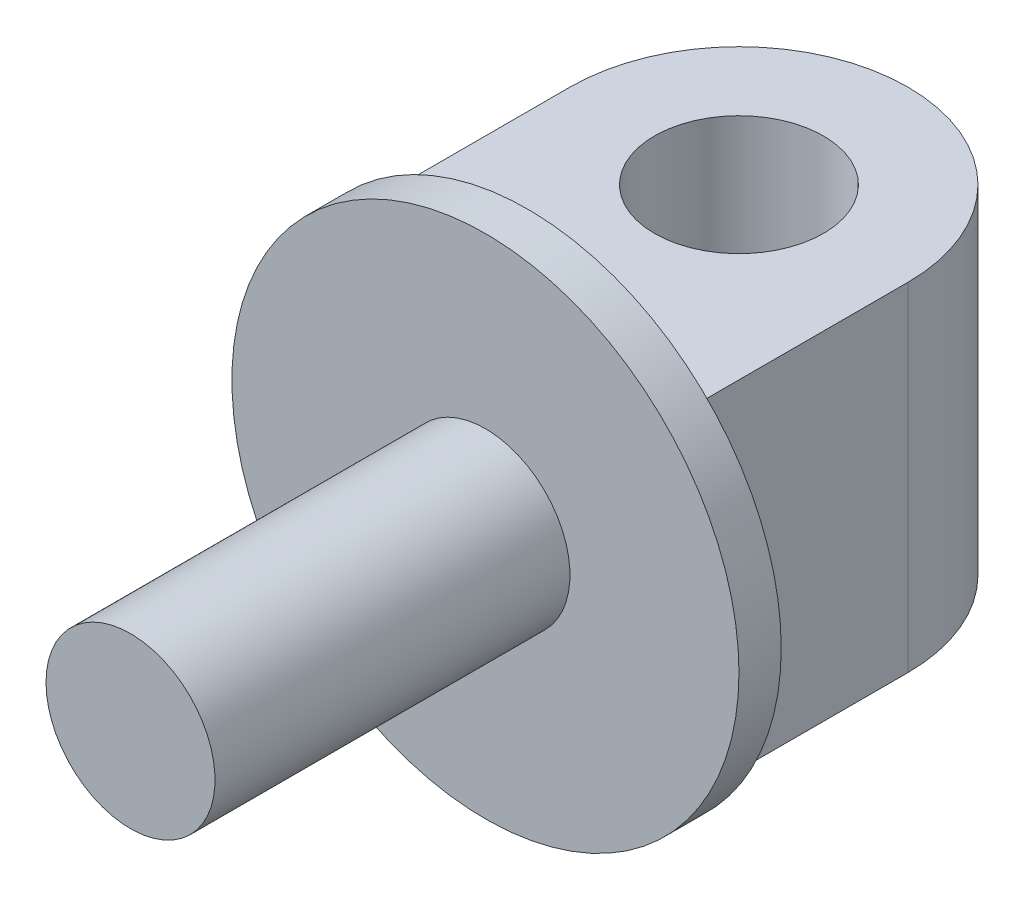
SolidWorks part; units mm, degrees
ref_plane "Front Plane" through (0, 0, 0) normal (0, 0, 1) x (1, 0, 0)
ref_plane "Top Plane" through (0, 0, 0) normal (0, 1, 0) x (1, 0, 0)
ref_plane "Right Plane" through (0, 0, 0) normal (1, 0, 0) x (0, 0, -1)
sketch "Cuff Stopper Sketch" plane through (0, 0, 0) normal (0, 0, 1) x (1, 0, 0)
  circle A0 centre (0, 0) radius 30
  dimension "D1" = 60
extrude "Cuff Stopper Extrude" add sketch "Cuff Stopper Sketch" against normal blind 5
sketch "Cuff Pin Sketch" plane through (0, 0, 0) normal (0, 0, 1) x (1, 0, 0)
  circle A0 centre (0, 0) radius 10
  dimension "D1" = 20
extrude "Cuff Pin Extrude" add sketch "Cuff Pin Sketch" along normal blind 42
sketch "Support Sketch" plane through (0, 0, -5) normal (0, 0, -1) x (-1, 0, 0)
  line L1 (-20, 20) -> (20, 20)
  line L2 (-20, 20) -> (-20, -20)
  line L3 (-20, -20) -> (20, -20)
  line L4 (20, 20) -> (20, -20)
  line L5 (-20, 20) -> (20, -20) construction
  line L6 (-20, -20) -> (20, 20) construction
  point P0 (0, 0)
  dimension "D1" = 40
extrude "Support Extrude" add sketch "Support Sketch" along normal blind 25
sketch "Pin Support Sketch" plane through (0, 0, 0) normal (0, 1, 0) x (1, 0, 0)
  line L0 (20, 30) -> (-20, 30)
  line L1 (-20, 30) -> (20, 30) construction
  arc A0 (20, 30) -> (-20, 30) centre (0, 30) ccw
extrude "Pin Support Extrude" add sketch "Pin Support Sketch" along normal up to surface and the other way up to surface up to face at (0, 20, -17.5) other way up to face at (0, -20, -17.5)
sketch "Pin Hole Sketch" plane through (0, 20, 0) normal (0, 1, 0) x (1, 0, 0)
  circle A0 centre (0, 30) radius 10
  arc A1 (20, 30) -> (-20, 30) centre (0, 30) ccw construction
  dimension "D1" = 20
extrude "Pin Hole Cut" cut sketch "Pin Hole Sketch" against normal up to surface (40 mm away) up to face at (0, -20, -22.5)
